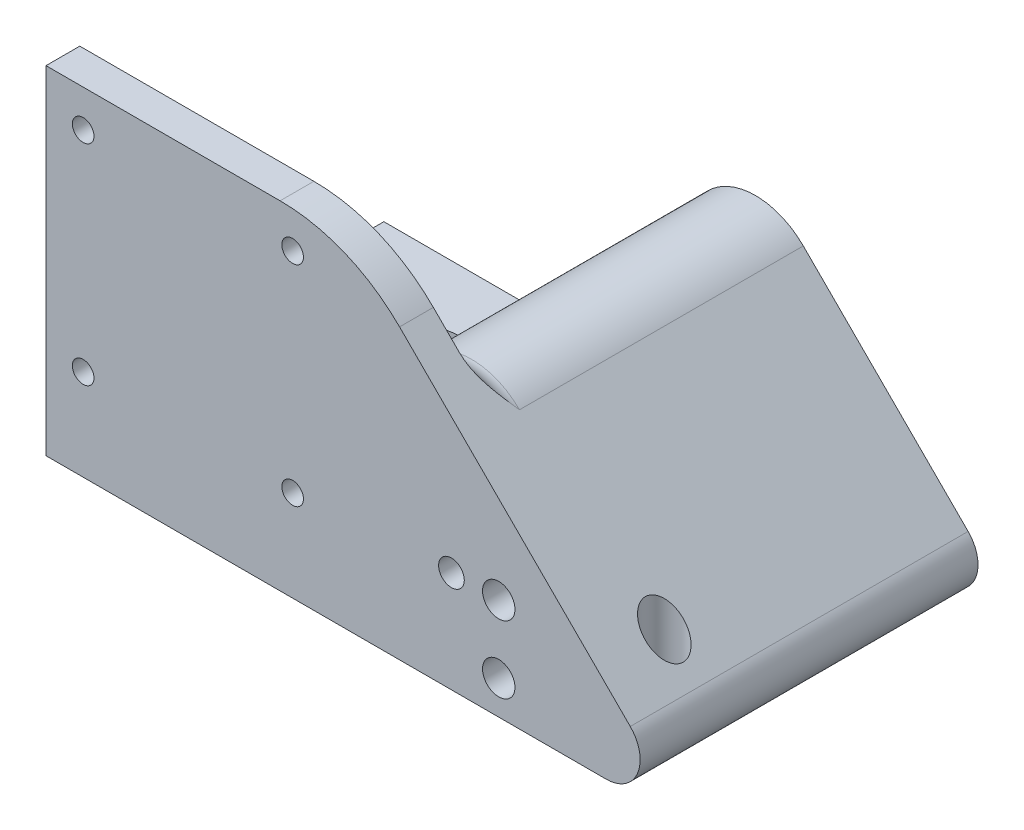
SolidWorks part; units mm, degrees
ref_plane "前视基准面" through (0, 0, 0) normal (0, 0, 1) x (1, 0, 0)
ref_plane "上视基准面" through (0, 0, 0) normal (0, 1, 0) x (1, 0, 0)
ref_plane "右视基准面" through (0, 0, 0) normal (1, 0, 0) x (0, 0, -1)
sketch "草图1" plane through (0, 0, 0) normal (0, 1, 0) x (1, 0, 0)
  line L0 (24, -24) -> (24, 21)
  line L1 (-21, -21) -> (21, -21) construction
  line L2 (-21, -21) -> (-21, 21)
  line L3 (-21, 21) -> (21, 21)
  line L4 (21, -21) -> (21, 21) construction
  line L5 (-21, -21) -> (21, 21) construction
  line L6 (-21, 21) -> (21, -21) construction
  line L7 (-15.5, -15.5) -> (15.5, -15.5) construction
  line L8 (-15.5, -15.5) -> (-15.5, 15.5) construction
  line L9 (-15.5, 15.5) -> (15.5, 15.5) construction
  line L10 (15.5, -15.5) -> (15.5, 15.5) construction
  line L11 (-15.5, -15.5) -> (15.5, 15.5) construction
  line L12 (-15.5, 15.5) -> (15.5, -15.5) construction
  line L13 (-21, -21) -> (21, -21) construction
  line L14 (-21, -21) -> (-21, -24)
  line L15 (-21, -24) -> (24, -24)
  line L17 (24, 21) -> (21, 21)
  circle A0 centre (-15.5, 15.5) radius 1.6
  circle A1 centre (15.5, 15.5) radius 1.6
  circle A2 centre (-15.5, -15.5) radius 1.6
  circle A3 centre (15.5, -15.5) radius 1.6
  circle A4 centre (0, 0) radius 12
  point P0 (0, 0)
  point P12 (0, 0)
  dimension "D3" = 3.2
  dimension "D4" = 3.2
  dimension "D5" = 3.2
  dimension "D6" = 3.2
  dimension "D9" = 24
  dimension "D1" = 42
  dimension "D2" = 42
  dimension "D7" = 31
  dimension "D8" = 3
  dimension "D10" = 3
extrude "凸台-拉伸1" add sketch "草图1" along normal blind 5
sketch "草图4" plane through (0, 0, 24) normal (0, 0, 1) x (1, 0, 0)
  line L0 (-21, 8) -> (21, 8) construction
  line L1 (-21, 0) -> (24, 0)
  line L2 (-21, 0) -> (-21, 50)
  line L3 (-21, 50) -> (24, 50)
  line L4 (24, 0) -> (24, 50)
  line L5 (21, 8) -> (-21, 50) construction
  line L8 (-15.5, 13.5) -> (15.5, 13.5) construction
  line L9 (-15.5, 13.5) -> (-15.5, 44.5) construction
  line L10 (-15.5, 44.5) -> (15.5, 44.5) construction
  line L11 (15.5, 13.5) -> (15.5, 44.5) construction
  line L12 (-15.5, 13.5) -> (15.5, 44.5) construction
  line L13 (-15.5, 44.5) -> (15.5, 13.5) construction
  circle A0 centre (-15.5, 44.5) radius 1.6
  circle A1 centre (15.5, 44.5) radius 1.6
  circle A2 centre (-15.5, 13.5) radius 1.6
  circle A3 centre (15.5, 13.5) radius 1.6
  point P7 (0, 29)
  dimension "D4" = 3.2
  dimension "D5" = 3.2
  dimension "D6" = 3.2
  dimension "D7" = 3.2
  dimension "D1" = 50
  dimension "D2" = 42
  dimension "D3" = 31
  dimension "D8" = 42
  dimension "D9" = 31
extrude "凸台-拉伸4" add sketch "草图4" along normal blind 5
sketch "草图5" plane through (24, 0, 0) normal (1, 0, 0) x (0, 0, -1)
  line L1 (21, 0) -> (-29, 0)
  line L2 (21, 0) -> (21, 50)
  line L3 (21, 50) -> (-29, 50)
  line L4 (-29, 0) -> (-29, 50)
extrude "凸台-拉伸5" add sketch "草图5" along normal blind 50
sketch "草图6" plane through (0, 0, -21) normal (0, 0, -1) x (-1, 0, 0)
  line L0 (-74, 0) -> (21, 0) construction
  line L1 (-24, 5) -> (-24, 50) construction
  circle A0 centre (-46, 5) radius 2.4
  circle A1 centre (-46, 15) radius 2.4
  circle A2 centre (-39, 15) radius 1.9
  circle A3 centre (-46, 5) radius 2 construction
  circle A4 centre (-46, 15) radius 2 construction
  circle A5 centre (-39, 15) radius 1.5 construction
  dimension "D1" = 5
  dimension "D2" = 10
  dimension "D3" = 15
  dimension "D4" = 7
  dimension "D6" = 4
  dimension "D7" = 4
  dimension "D8" = 3
  dimension "D9" = 7
  dimension "D5" = 15
  dimension "D10" = 0.4
extrude "切除-拉伸1" cut sketch "草图6" against normal through all
sketch "草图7" plane through (0, 0, 0) normal (0, -1, 0) x (1, 0, 0)
  line L0 (-21, 29) -> (74, 29) construction
  line L1 (-21, -21) -> (-21, 29) construction
  circle A1 centre (60.5, 19) radius 1.8
  dimension "D1" = 3.6
  dimension "D2" = 10
  dimension "D3" = 81.5
extrude "切除-拉伸2" cut sketch "草图7" against normal through all
sketch "草图8" plane through (0, 50, 0) normal (0, 1, 0) x (1, 0, 0)
  circle A0 centre (60.5, -19) radius 1.8 construction
  circle A1 centre (60.5, -19) radius 1.8 construction
  circle A2 centre (60.5, -19) radius 2.8
  dimension "D1" = 1
extrude "切除-拉伸3" cut sketch "草图8" against normal offset from surface (45 mm away) 5 up to face at (60.5, 0, 17.2)
sketch "草图9" plane through (0, 0, -21) normal (0, 0, -1) x (-1, 0, 0)
  line L0 (-74, 0) -> (21, 0) construction
  line L1 (-51, 0) -> (-34, 0)
  line L2 (-51, 0) -> (-51, 20)
  line L3 (-51, 20) -> (-34, 20)
  line L4 (-34, 0) -> (-34, 20)
  line L5 (-24, 5) -> (-24, 50) construction
  dimension "D1" = 10
  dimension "D2" = 17
  dimension "D3" = 20
extrude "切除-拉伸4" cut sketch "草图9" against normal offset from surface (45 mm away) 5 up to face at (43.6, 5, 29)
chamfer "倒角1" distance 50 angle 45 1 edges at (74, 50, 4)
fillet "圆角1" radius 5 1 edges at (74, 0, 4)
fillet "圆角4" radius 10 1 edges at (24, 50, 1.5) type face fillet first side face at (40.5858, 33.4142, 8) second side face at (24, 27.5, 1.5)
fillet "圆角5" radius 25 1 edges at (24, 50, 26.5)
fillet "圆角6" radius 3 6 edges at (1.5, 5, 24) (24, 5, 1.5) (30.1732, 35.0967, 24) (24, 15.4289, 24) (34, 20, 1.5) (51, 20, 1.5)
fillet "圆角7" radius 1.5 5 edges at (51, 8.5, 24) (50.1213, 19.1213, 24) (34, 8.5, 24) (34.8787, 19.1213, 24) (42.5, 20, 24)
